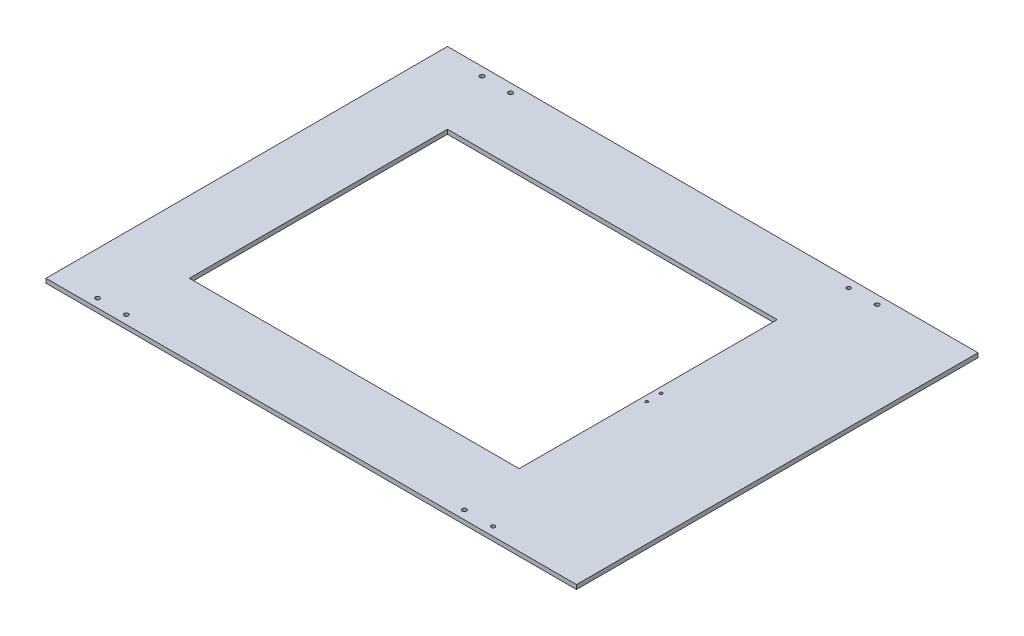
SolidWorks part; units mm, degrees
ref_plane "Front Plane" through (0, 0, 0) normal (0, 0, 1) x (1, 0, 0)
ref_plane "Top Plane" through (0, 0, 0) normal (0, 1, 0) x (1, 0, 0)
ref_plane "Right Plane" through (0, 0, 0) normal (1, 0, 0) x (0, 0, -1)
sketch "Sketch1" plane through (0, 0, 0) normal (0, 1, 0) x (1, 0, 0)
  line L1 (0, 0) -> (370, 0)
  line L2 (0, 0) -> (0, 280)
  line L3 (0, 280) -> (370, 280)
  line L4 (370, 0) -> (370, 280)
  line L5 (50, 50) -> (280, 50)
  line L6 (50, 50) -> (50, 230)
  line L7 (50, 230) -> (280, 230)
  line L8 (280, 50) -> (280, 230)
  line L9 (50, 280) -> (50, 274) construction
  line L10 (50, 274) -> (30, 274) construction
  line L12 (185, 280) -> (185, 0) construction
  line L13 (0, 140) -> (370, 140) construction
  line L14 (284, 140) -> (284, 145) construction
  line L15 (284, 140) -> (284, 135) construction
  circle A0 centre (30, 274) radius 1.5
  circle A1 centre (50, 274) radius 1.5692
  circle A2 centre (30, 6) radius 1.5
  circle A3 centre (50, 6) radius 1.5
  circle A4 centre (285.7569, 273.9854) radius 1.3573
  circle A5 centre (305.7569, 273.9346) radius 1.5
  circle A6 centre (285.7569, 6.0015) radius 1.5
  circle A7 centre (305.7569, 6.0068) radius 1.3225
  circle A8 centre (284, 145) radius 1
  circle A9 centre (284, 135) radius 1
  point P9 (305.7569, 6.0015)
  point P10 (305.7569, 273.9854)
  dimension "D11" = 3
  dimension "D12" = 2
  dimension "D1" = 370
  dimension "D2" = 280
  dimension "D3" = 230
  dimension "D4" = 50
  dimension "D5" = 50
  dimension "D6" = 50
  dimension "D8" = 6
  dimension "D10" = 20
  dimension "D13" = 4
  dimension "D14" = 10
  dimension "D15" = 20
  dimension "D16" = 20
  dimension "D17" = 20
extrude "Boss-Extrude1" add sketch "Sketch1" along normal blind 3
